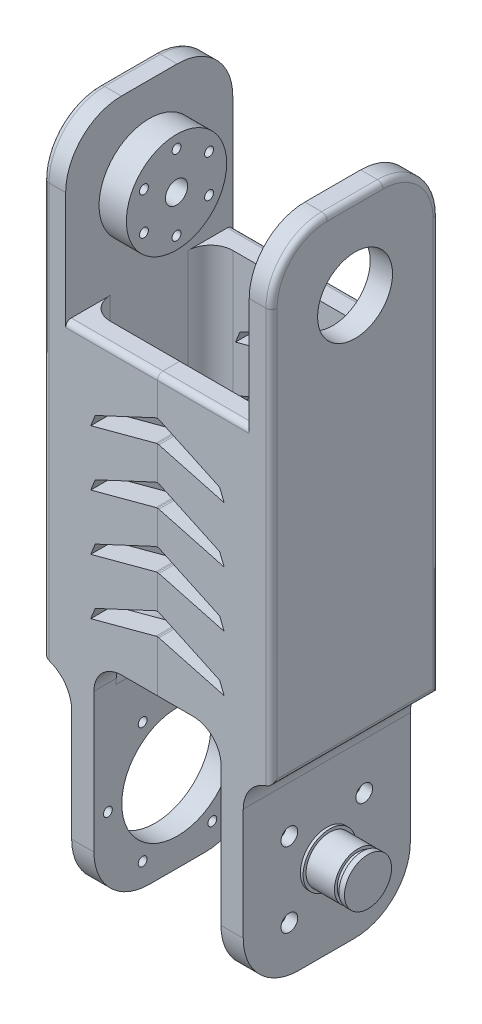
SolidWorks part; units mm, degrees
other "标注1"
sketch "草图21" plane through (0, -160, -30) normal (-0.4801, -0.1175, -0.8693) x (-0.746, 0.5761, 0.3342)
material "PETG-CF"
ref_plane "前视基准面" through (0, 0, 0) normal (0, 0, 1) x (1, 0, 0)
ref_plane "上视基准面" through (0, 0, 0) normal (0, 1, 0) x (1, 0, 0)
ref_plane "右视基准面" through (0, 0, 0) normal (1, 0, 0) x (0, 0, -1)
other "Configuration Table"
sketch "草图1" plane through (0, 0, 0) normal (1, 0, 0) x (0, 0, -1)
  line L1 (30, -80) -> (-30, -80)
  line L2 (30, -80) -> (30, 80)
  line L3 (30, 80) -> (-30, 80)
  line L4 (-30, -80) -> (-30, 80)
  line L5 (30, -80) -> (-30, 80) construction
  line L6 (30, 80) -> (-30, -80) construction
  point P0 (0, 0)
  dimension "D1" = 160
  dimension "D2" = 60
extrude "凸台-拉伸1" add sketch "草图1" along normal blind 8
sketch "草图2" plane through (8, 0, 0) normal (1, 0, 0) x (0, 0, -1)
  line L1 (30, 80) -> (-30, 80) construction
  circle A0 centre (0, 50) radius 13.5 construction
  circle A2 centre (0, 63.5) radius 1.6
  circle A4 centre (11.6913, 56.75) radius 1.6
  circle A5 centre (11.6913, 43.25) radius 1.6
  circle A6 centre (0, 36.5) radius 1.6
  circle A7 centre (-11.6913, 43.25) radius 1.6
  circle A8 centre (-11.6913, 56.75) radius 1.6
  circle A12 centre (0, 50) radius 4
  point P6 (0, 80)
  point P26 (0, 50)
  dimension "D3" = 27
  dimension "D7" = 3.2
  dimension "D11" = 8
  dimension "D2" = 30
  dimension "D9" = 6
extrude "切除-拉伸1" cut sketch "草图2" against normal through all
sketch "草图20" plane through (8, 0, 0) normal (1, 0, 0) x (0, 0, -1)
  circle A0 centre (0, 50) radius 18
  dimension "D1" = 36
extrude "凸台-拉伸7" add sketch "草图20" along normal blind 9.8
sketch "草图3" plane through (8, 0, 0) normal (1, 0, 0) x (0, 0, -1)
  line L0 (-30, 80) -> (-30, -80) construction
  line L1 (-22, -80) -> (-30, -80)
  line L2 (-22, -80) -> (-22, 20)
  line L3 (-22, 20) -> (-30, 20)
  line L4 (-30, -80) -> (-30, 20)
  line L5 (-22, -80) -> (-30, 20) construction
  line L6 (-22, 20) -> (-30, -80) construction
  line L7 (30, -80) -> (22, -80)
  line L8 (30, -80) -> (30, 20)
  line L9 (30, 20) -> (22, 20)
  line L10 (22, -80) -> (22, 20)
  line L11 (30, -80) -> (22, 20) construction
  line L12 (30, 20) -> (22, -80) construction
  line L13 (30, -80) -> (30, 80) construction
  line L14 (30, 80) -> (-30, 80) construction
  line L16 (-30, -80) -> (30, -80) construction
  point P0 (-26, -30)
  point P5 (26, -30)
  dimension "D1" = 60
  dimension "D3" = 60
  dimension "D5" = 8
  dimension "D6" = 8
extrude "凸台-拉伸2" add sketch "草图3" along normal blind 65.9
sketch "草图4" plane through (73.9, 0, 0) normal (1, 0, 0) x (0, 0, -1)
  line L0 (30, -80) -> (-30, 80) construction
  line L1 (30, -80) -> (-30, -80)
  line L2 (30, -80) -> (30, 80)
  line L3 (30, 80) -> (-30, 80)
  line L4 (-30, -80) -> (-30, 80)
  line L5 (30, -80) -> (-30, 80) construction
  line L6 (30, 80) -> (-30, -80) construction
  line L7 (30, 80) -> (-30, 80) construction
  point P0 (0, 0)
extrude "凸台-拉伸3" add sketch "草图4" along normal blind 8
sketch "草图9" plane through (73.9, 0, 0) normal (-1, 0, 0) x (0, 0, 1)
  circle A0 centre (0, 50) radius 13.45
  dimension "D1" = 26.9
extrude "切除-拉伸5" cut sketch "草图9" against normal up to next
sketch "草图11" plane through (0, 0, 30) normal (0, 0, 1) x (1, 0, 0)
  line L0 (0, 80) -> (0, -80) construction
  line L1 (0, -80) -> (18.15, -80)
  line L2 (0, -80) -> (0, -88)
  line L3 (0, -88) -> (18.15, -88)
  line L4 (18.15, -80) -> (18.15, -88)
  line L5 (81.9, -80) -> (63.75, -80)
  line L6 (81.9, -80) -> (81.9, -88)
  line L7 (81.9, -88) -> (63.75, -88)
  line L8 (63.75, -80) -> (63.75, -88)
  line L9 (81.9, 80) -> (81.9, -80) construction
  line L11 (18.15, -88) -> (10.15, -88)
  line L12 (18.15, -88) -> (18.15, -160)
  line L13 (18.15, -160) -> (10.15, -160)
  line L14 (10.15, -88) -> (10.15, -160)
  line L15 (63.75, -88) -> (71.75, -88)
  line L16 (63.75, -88) -> (63.75, -160)
  line L17 (63.75, -160) -> (71.75, -160)
  line L18 (71.75, -88) -> (71.75, -160)
  line M10 (0, -80) -> (81.9, -80)
  dimension "D1" = 8
  dimension "D2" = 8
  dimension "D3" = 45.6
  dimension "D4" = 72
  dimension "D5" = 72
  dimension "D6" = 8
  dimension "D7" = 8
extrude "凸台-拉伸4" add sketch "草图11" against normal blind 60 contours L3 L14 L13 L12 | L4 L2 L3 M10 | L8 L7 L6 M10 | L18 L7 L16 L17 region at (72.825, -84, 30) region at (9.075, -84, 30) region at (14.15, -124, 30) region at (67.75, -124, 30)
fillet "圆角1" radius 20 8 edges at (4, 80, -30) (4, 80, 30) (77.9, 80, -30) (77.9, 80, 30) (67.75, -160, -30) (67.75, -160, 30) (14.15, -160, -30) (14.15, -160, 30)
fillet "圆角2" radius 12 4 edges at (63.75, -80, 0) (18.15, -80, 0) (71.75, -88, 0) (10.15, -88, 0)
sketch "草图13" plane through (71.75, 0, 0) normal (1, 0, 0) x (0, 0, -1)
  line L0 (10, -160) -> (-10, -160) construction
  line L1 (0, -130) -> (13.435, -116.565) construction
  line L3 (0, -130) -> (0, -111) construction
  circle A0 centre (0, -130) radius 19 construction
  circle A1 centre (13.435, -116.565) radius 1.6
  circle A2 centre (13.435, -143.435) radius 1.6
  circle A3 centre (-13.435, -143.435) radius 1.6
  circle A4 centre (-13.435, -116.565) radius 1.6
  point P4 (0, -160)
  point P5 (0.0241, -160.1066)
  point P17 (0, -130)
  dimension "D1" = 38
  dimension "D3" = 3.2
  dimension "D2" = 30
  dimension "D5" = 45
  dimension "D4" = 4
extrude "切除-拉伸6" cut sketch "草图13" against normal up to next
sketch "草图12" plane through (10.15, 0, 0) normal (-1, 0, 0) x (0, 0, 1)
  circle A0 centre (0, -130) radius 25 construction
  circle A1 centre (-12.5, -108.3494) radius 1.6
  circle A2 centre (12.5, -108.3494) radius 1.6
  circle A3 centre (25, -130) radius 1.6
  circle A4 centre (12.5, -151.6506) radius 1.6
  circle A5 centre (-12.5, -151.6506) radius 1.6
  circle A6 centre (-25, -130) radius 1.6
  circle A7 centre (0, -130) radius 20
  point P17 (0, -130)
  dimension "D1" = 50
  dimension "D2" = 3.2
  dimension "D4" = 40
  dimension "D3" = 6
sketch "草图14" plane through (71.75, 0, 0) normal (1, 0, 0) x (0, 0, -1)
  circle A0 centre (0, -130) radius 8.45
  dimension "D1" = 16.9
extrude "凸台-拉伸5" add sketch "草图14" along normal blind 14.8
ref_plane "基准面1" through (84.55, 0, 0) normal (1, 0, 0) x (0, 0, -1)
sketch "草图15" plane through (84.55, 0, 0) normal (1, 0, 0) x (0, 0, -1)
  circle A0 centre (0, -130) radius 8.45
  circle A1 centre (0, -130) radius 7.45
  dimension "D1" = 16.9
  dimension "D2" = 14.9
extrude "切除-拉伸7" cut sketch "草图15" against normal blind 1.6
extrude "切除-拉伸8" cut sketch "草图12" against normal up to next
sketch "草图16" plane through (0, 0, 0) normal (-1, 0, 0) x (0, 0, 1)
  circle A0 centre (0, 63.5) radius 3
  circle A1 centre (11.6913, 56.75) radius 3
  circle A2 centre (11.6913, 43.25) radius 3
  circle A3 centre (0, 36.5) radius 3
  circle A4 centre (-11.6913, 43.25) radius 3
  circle A5 centre (-11.6913, 56.75) radius 3
  point P17 (0, 50)
  dimension "D1" = 6
  dimension "D2" = 6
extrude "切除-拉伸9" cut sketch "草图16" against normal blind 4
sketch "草图17" plane through (10.15, 0, 0) normal (-1, 0, 0) x (0, 0, 1)
  circle A0 centre (-12.5, -108.3494) radius 3
  circle A1 centre (12.5, -108.3494) radius 3
  circle A2 centre (25, -130) radius 3
  circle A3 centre (12.5, -151.6506) radius 3
  circle A4 centre (-12.5, -151.6506) radius 3
  circle A5 centre (-25, -130) radius 3
  point P15 (0, -130)
  dimension "D1" = 6
  dimension "D2" = 6
extrude "切除-拉伸10" cut sketch "草图17" against normal blind 4
sketch "草图18" plane through (71.75, 0, 0) normal (1, 0, 0) x (0, 0, -1)
  circle A0 centre (13.435, -116.565) radius 3
  circle A1 centre (13.435, -143.435) radius 3
  circle A2 centre (-13.435, -143.435) radius 3
  circle A3 centre (-13.435, -116.565) radius 3
  point P12 (0, -130)
  dimension "D1" = 6
  dimension "D2" = 4
extrude "切除-拉伸11" cut sketch "草图18" against normal blind 4
sketch "草图19" plane through (71.75, 0, 0) normal (1, 0, 0) x (0, 0, -1)
  circle A0 centre (0, -130) radius 9.5
  dimension "D1" = 19
extrude "凸台-拉伸6" add sketch "草图19" along normal blind 1
extrude "切除-拉伸12" cut sketch "草图2<3>" along normal up to next
sketch "草图2<3>" plane through (8, 0, 0) normal (1, 0, 0) x (0, 0, -1) same geometry as "草图2"
fillet "圆角3" radius 8 4 edges at (8, -30, -22) (8, -30, 22) (73.9, -30, 22) (73.9, -30, -22)
fillet "圆角4" radius 2 14 edges at (81.9, -14, 30) (81.9, 74.1421, 24.1421) (81.9, 80, 0) (81.9, 74.1421, -24.1421) (81.9, -14, -30) (0, -14, 30) (0, 74.1421, 24.1421) (0, 80, 0) (0, 74.1421, -24.1421) (81.9, -88, 0) (0, -88, 0) (40.95, 20, 30) (40.95, 20, -30) (0, -14, -30)
fillet "圆角5" radius 10 2 edges at (18.15, -80, -26) (63.75, -80, -26)
ref_plane "基准面2" through (40.95, 0, 0) normal (1, 0, 0) x (0, 0, -1)
sketch "草图25" plane through (0, 0, -30) normal (0, 0, -1) x (-1, 0, 0)
  line L1 (-41.7952, -53.9768) -> (-63.2902, -64)
  line L7 (-40.95, 30.8) -> (-40.95, -30.8) construction
  line L8 (-63.2902, -64) -> (-64.9, -68)
  line L9 (-64.9, -68) -> (-41.4676, -61.7213)
  line L11 (-40.4324, -61.7213) -> (-17, -68)
  line L12 (-17, -68) -> (-18.6098, -64)
  line L13 (-18.6098, -64) -> (-40.1048, -53.9768)
  line L14 (-2, -88.4909) -> (-2, 60) construction
  line L15 (-53.75, -80) -> (-28.15, -80) construction
  arc A0 (-41.4676, -61.7213) -> (-40.4324, -61.7213) centre (-40.95, -63.6532) cw
  arc A1 (-41.7952, -53.9768) -> (-40.1048, -53.9768) centre (-40.95, -55.7894) cw
  point P16 (-40.95, -61.5826)
  point P19 (-40.95, -53.5826)
  dimension "D7" = 2
  dimension "D2" = 8
  dimension "D1" = 4
  dimension "D3" = 65
  dimension "D4" = 65
  dimension "D5" = 12
  dimension "D6" = 15
  dimension "D8" = 150
extrude "切除-拉伸13" cut sketch "草图25" against normal through all
pattern_linear "阵列(线性)1" count 4 spacing 20 along (0, 1, 0) of "切除-拉伸13"
split "分割1" trim tools "基准面2" bodies to split 130 resulting bodies 127 128
